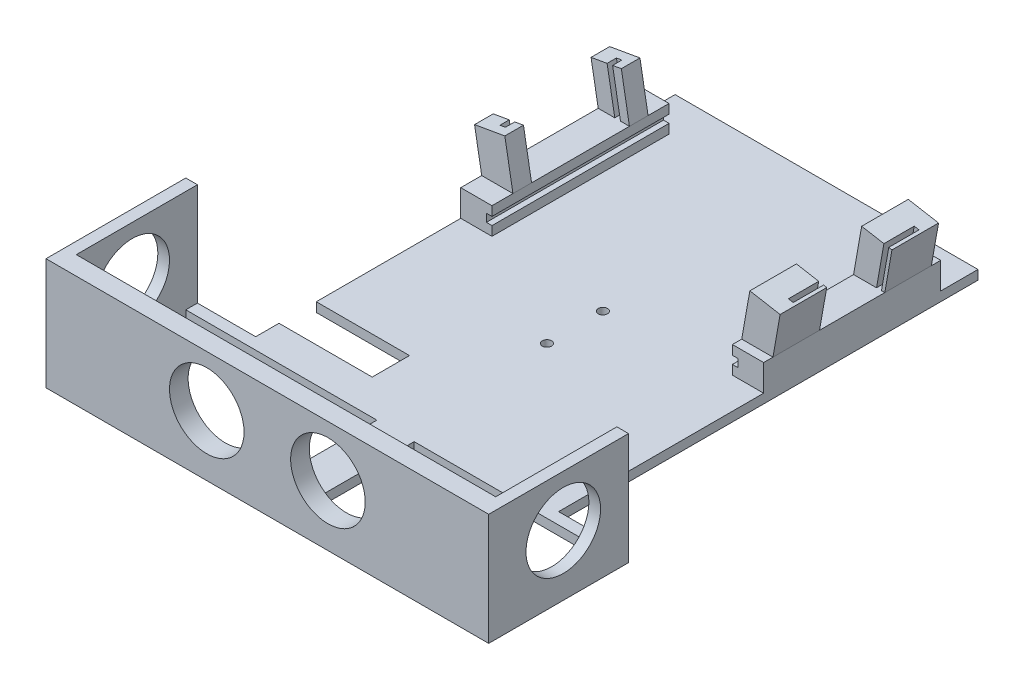
SolidWorks part; units mm, degrees
ref_plane "Front Plane" through (0, 0, 0) normal (0, 0, 1) x (1, 0, 0)
ref_plane "Top Plane" through (0, 0, 0) normal (0, 1, 0) x (1, 0, 0)
ref_plane "Right Plane" through (0, 0, 0) normal (1, 0, 0) x (0, 0, -1)
sketch "Sketch1" plane through (0, 0, 0) normal (0, 0, 1) x (1, 0, 0)
  line L0 (55, 0) -> (-55, 0) construction
  line L1 (47.5, -11) -> (-47.5, -11)
  line L2 (47.5, -11) -> (47.5, 11)
  line L3 (47.5, 11) -> (-47.5, 11)
  line L4 (-47.5, -11) -> (-47.5, 11)
  line L5 (47.5, -11) -> (-47.5, 11) construction
  line L6 (47.5, 11) -> (-47.5, -11) construction
  circle A0 centre (-13, 0) radius 8
  circle A1 centre (13, 0) radius 8
  point P0 (0, 0)
  dimension "D3" = 16
  dimension "D4" = 16
  dimension "D1" = 26
  dimension "D2" = 13
  dimension "D5" = 95
  dimension "D6" = 22
extrude "Boss-Extrude1" add sketch "Sketch1" along normal blind 4
ref_plane "Plane1" through (0, -11, 0) normal (0, -1, 0) x (-1, 0, 0)
sketch "Sketch2" plane through (0, -11, 0) normal (0, -1, 0) x (-1, 0, 0)
  line L0 (0, 2.2) -> (0, -2.2) construction
  line L1 (-32.5, 116) -> (32.5, 116)
  line L3 (-32.5, -4) -> (32.5, -4)
  line L4 (32.5, 116) -> (32.5, 39)
  line L5 (-32.5, 116) -> (32.5, -4) construction
  line L6 (-32.5, -4) -> (-17.6042, 23.5) construction
  line L7 (47.5, -4) -> (-47.5, -4) construction
  line L13 (-32.5, -4) -> (-47.5, -4)
  line L14 (-32.5, 26) -> (-47.5, 26)
  line L15 (-47.5, -4) -> (-47.5, 26)
  line L16 (32.5, 26) -> (47.5, 26)
  line L17 (47.5, 26) -> (47.5, -4)
  line L18 (47.5, -4) -> (32.5, -4)
  line L19 (-45, 23.5) -> (-45, 0)
  line L20 (-45, 23.5) -> (-4, 23.5)
  line L21 (-45, 0) -> (-4, 0)
  line L22 (45, 23.5) -> (45, 0)
  line L23 (47.5, 0) -> (-47.5, 0) construction
  line L24 (4, 0) -> (4, 23.5)
  line L27 (-4, 0) -> (-4, 23.5)
  line L28 (4, 23.5) -> (45, 23.5)
  line L29 (4, 0) -> (45, 0)
  line L36 (32.5, 39) -> (12.5, 39)
  line L37 (32.5, 31) -> (12.5, 31)
  line L38 (12.5, 39) -> (12.5, 31)
  line L39 (32.5, 31) -> (32.5, 26)
  line L40 (0, 56) -> (32.5, 116) construction
  line L41 (-32.5, 116) -> (-32.5, 26)
  point P0 (0, 56)
  dimension "D1" = 65
  dimension "D2" = 120
  dimension "D3" = 15
  dimension "D4" = 30
  dimension "D5" = 15
  dimension "D6" = 15
  dimension "D7" = 15
  dimension "D8" = 2.5
  dimension "D9" = 2.5
  dimension "D10" = 0
  dimension "D11" = 2.5
  dimension "D12" = 4
  dimension "D13" = 4
  dimension "D15" = 20
  dimension "D18" = 8
  dimension "D19" = 5
extrude "Boss-Extrude2" add sketch "Sketch2" along normal blind 2
sketch "Sketch4" plane through (0, 0, 0) normal (0, 0, 1) x (1, 0, 0)
  line L0 (-25.8, -11) -> (-25.8, -9)
  line L1 (-55, -11) -> (55, -11) construction
  line L2 (-25.8, -9) -> (-27, -9)
  line L3 (-27, -9) -> (-27, -7.3)
  line L4 (-27, -7.3) -> (-25.8, -7.3)
  line L5 (-25.8, -7.3) -> (-25.8, -5.3)
  line L6 (-25.8, -5.3) -> (-32.5, -5.3)
  line L7 (-32.5, -5.3) -> (-32.5, -11)
  line L8 (-32.5, -11) -> (-25.8, -11)
  line L9 (0, -21.4873) -> (0, 18.1435) construction
  line L10 (0, -2.2) -> (0, 2.2) construction
  line L11 (32.5, -5.3) -> (32.5, -11)
  line L12 (32.5, -11) -> (25.8, -11)
  line L13 (25.8, -11) -> (25.8, -9)
  line L14 (25.8, -9) -> (27, -9)
  line L15 (27, -9) -> (27, -7.3)
  line L16 (27, -7.3) -> (25.8, -7.3)
  line L17 (25.8, -7.3) -> (25.8, -5.3)
  line L18 (25.8, -5.3) -> (32.5, -5.3)
  line L19 (-32.5, -13) -> (-32.5, -11) construction
  dimension "D1" = 1.7
  dimension "D2" = 2
  dimension "D3" = 2
  dimension "D4" = 27
  dimension "D5" = 1.2
extrude "Boss-Extrude3" add sketch "Sketch4" against normal blind 38 from offset 70 offset against normal yes
sketch "Sketch5" plane through (0, -13, 0) normal (0, -1, 0) x (1, 0, 0)
  line L0 (-32.5, 14) -> (32.5, -106) construction
  line L1 (32.5, 14) -> (-32.5, -106) construction
  line L2 (0, -14.3) -> (0, 14.3) construction
  line L4 (-47.5, 4) -> (-47.5, -26) construction
  line L6 (-47.5, -26) -> (-32.5, -26) construction
  circle A0 centre (-15, -56) radius 1.2
  circle A1 centre (15, -56) radius 1.2
  circle A2 centre (15, -68) radius 1.2
  circle A3 centre (-15, -68) radius 1.2
  point P10 (0, -46)
  dimension "D1" = 2.4
  dimension "D4" = 2.4
  dimension "D7" = 2.4
  dimension "D8" = 2.4
  dimension "D2" = 12
  dimension "D3" = 15
  dimension "D5" = 10
  dimension "D6" = 15
  dimension "D9" = 65
  dimension "D10" = 120
  dimension "D11" = 15
  dimension "D12" = 40
ref_plane "Plane2" through (0.1284, -0.7281, 0) normal (-0.1736, 0.9848, 0) x (0, 0, 1)
sketch "Sketch7" plane through (0.1284, -0.7281, 0) normal (-0.1736, 0.9848, 0) x (0, 0, 1)
  line L0 (-74.5, -26.3284) -> (-74.5, -32.9266)
  line L1 (-108, -26.3284) -> (-70, -26.3284) construction
  line L2 (-108, -32.9266) -> (-70, -32.9266) construction
  line L3 (-74.5, -32.9266) -> (-78.5, -32.9266)
  line L4 (-78.5, -32.9266) -> (-78.5, -29.4266)
  line L5 (-78.5, -29.4266) -> (-76.5, -29.4266)
  line L6 (-76.5, -29.4266) -> (-76.5, -28.2266)
  line L7 (-76.5, -28.2266) -> (-78.5, -28.2266)
  line L8 (-78.5, -28.2266) -> (-78.5, -26.3284)
  line L9 (-78.5, -26.3284) -> (-74.5, -26.3284)
  line L10 (-89, -32.9266) -> (-89, 11.3249) construction
  line L11 (-101.5, -28.2266) -> (-99.5, -28.2266)
  line L12 (-101.5, -29.4266) -> (-101.5, -28.2266)
  line L13 (-99.5, -29.4266) -> (-101.5, -29.4266)
  line L14 (-99.5, -32.9266) -> (-99.5, -29.4266)
  line L15 (-103.5, -32.9266) -> (-99.5, -32.9266)
  line L16 (-103.5, -26.3284) -> (-103.5, -32.9266)
  line L17 (-99.5, -26.3284) -> (-103.5, -26.3284)
  line L18 (-99.5, -28.2266) -> (-99.5, -26.3284)
  dimension "D1" = 1.2
  dimension "D2" = 2
  dimension "D3" = 2
  dimension "D4" = 12.5
  dimension "D5" = 3.5
extrude "Boss-Extrude5" add sketch "Sketch7" along normal blind 10
ref_plane "Plane3" through (-0.1284, -0.7281, 0) normal (0.1736, 0.9848, 0) x (0, 0, 1)
sketch "Sketch8" plane through (-0.1284, -0.7281, 0) normal (0.1736, 0.9848, 0) x (0, 0, 1)
  line L0 (-82, 26.3284) -> (-82, 31.1766)
  line L1 (-108, 26.3284) -> (-70, 26.3284) construction
  line L2 (-82, 31.1766) -> (-75.5, 31.1766)
  line L3 (-75.5, 31.1766) -> (-75.5, 32.2266)
  line L4 (-75.5, 32.2266) -> (-82, 32.2266)
  line L5 (-82, 32.2266) -> (-82, 32.9266)
  line L6 (-108, 32.9266) -> (-70, 32.9266) construction
  line L7 (-82, 32.9266) -> (-72, 32.9266)
  line L8 (-72, 32.9266) -> (-72, 26.3284)
  line L9 (-72, 26.3284) -> (-82, 26.3284)
  line L10 (-89, 26.3284) -> (-89, 55.5373) construction
  line L11 (-96, 32.2266) -> (-96, 32.9266)
  line L12 (-96, 31.1766) -> (-102.5, 31.1766)
  line L13 (-102.5, 31.1766) -> (-102.5, 32.2266)
  line L14 (-102.5, 32.2266) -> (-96, 32.2266)
  line L15 (-96, 32.9266) -> (-106, 32.9266)
  line L16 (-106, 32.9266) -> (-106, 26.3284)
  line L17 (-106, 26.3284) -> (-96, 26.3284)
  line L18 (-96, 26.3284) -> (-96, 31.1766)
  dimension "D1" = 1.05
  dimension "D2" = 0.7
  dimension "D3" = 7
  dimension "D4" = 10
  dimension "D5" = 6.5
extrude "Boss-Extrude6" add sketch "Sketch8" along normal blind 10
sketch "Sketch10" plane through (0, -13, 0) normal (0, -1, 0) x (1, 0, 0)
  line L0 (0, -14.3) -> (0, 14.3) construction
  circle A0 centre (0, -56) radius 1
  circle A2 centre (0, -68) radius 1
  dimension "D1" = 2
  dimension "D2" = 2
extrude "Cut-Extrude1" cut sketch "Sketch10" against normal blind 4
sketch "Sketch11" plane through (0, 0, 0) normal (1, 0, 0) x (0, 0, -1)
  line L0 (-4, 11) -> (-4, -13)
  line L1 (-4, 11) -> (26, 11)
  line L2 (-4, -13) -> (26, -13)
  line L3 (26, 11) -> (26, -13)
  line L4 (52.25, 0) -> (-52.25, 0) construction
  line L5 (-14, -13) -> (106, -13) construction
  circle A0 centre (12, 0) radius 8
  dimension "D1" = 14
  dimension "D2" = 16
  dimension "D4" = 30
extrude "Boss-Extrude11" add sketch "Sketch11" along normal blind 2.5 from offset 45
extrude "Boss-Extrude12" add sketch "Sketch11<2>" against normal blind 2.5 from offset 45 offset against normal yes
sketch "Sketch11<2>" plane through (0, 0, 0) normal (1, 0, 0) x (0, 0, -1) same geometry as "Sketch11"
